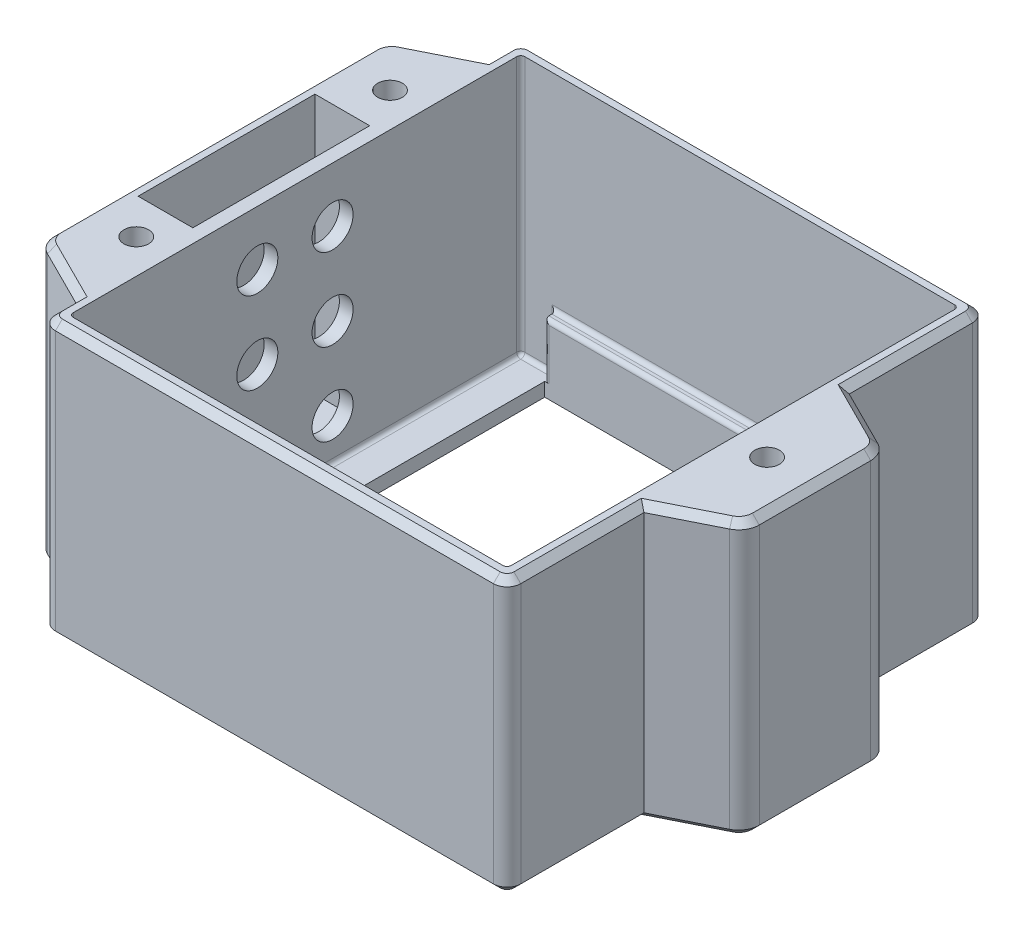
SolidWorks part; units mm, degrees
ref_plane "Front Plane" through (0, 0, 0) normal (0, 0, 1) x (1, 0, 0)
ref_plane "Top Plane" through (0, 0, 0) normal (0, 1, 0) x (1, 0, 0)
ref_plane "Right Plane" through (0, 0, 0) normal (1, 0, 0) x (0, 0, -1)
sketch "Sketch1" plane through (0, 0, 0) normal (0, 1, 0) x (1, 0, 0)
  line L0 (0, 36.2903) -> (0, -48.3871) construction
  line L1 (-53.2258, 0) -> (72.1774, 0) construction
  line L3 (-32, 35) -> (32, 35)
  line L4 (-34, 33) -> (-34, -33)
  line L5 (-32, -35) -> (32, -35)
  line L6 (34, 33) -> (34, -33)
  arc A0 (32, 35) -> (34, 33) centre (32, 33) cw
  arc A1 (32, -35) -> (34, -33) centre (32, -33) ccw
  arc A2 (-34, -33) -> (-32, -35) centre (-32, -33) ccw
  arc A3 (-32, 35) -> (-34, 33) centre (-32, 33) ccw
  point P9 (-50, 28.8306)
  point P10 (0, 0)
  point P11 (0, 0)
  point P14 (34, 35)
  point P17 (34, -35)
  point P22 (-34, 35)
  dimension "D3" = 2
  dimension "D1" = 68
  dimension "D2" = 70
extrude "Boss-Extrude1" add sketch "Sketch1" along normal blind 40
shell "Shell1" thickness 2 removed face at (0, 40, 0)
sketch "Sketch2" plane through (0, 0, 0) normal (0, 1, 0) x (1, 0, 0)
  line L1 (-34, 30) -> (-42.3416, 25.8292)
  line L2 (-44, 23.1459) -> (-44, -23.1459)
  line L3 (-42.3416, -25.8292) -> (-34, -30)
  line L4 (34, 15) -> (42.3416, 10.8292)
  line L6 (44, 8.1459) -> (44, -8.1459)
  line L7 (42.3416, -10.8292) -> (34, -15)
  line L9 (38.345, 0) -> (52.7567, 0) construction
  line L10 (-59.946, 0) -> (-25.6629, 0) construction
  line L11 (-34, 30) -> (-34, -30)
  line L12 (34, -15) -> (34, 15)
  line L13 (-1.2597, 0) -> (7.6725, 0) construction
  circle A0 centre (-37, 18.8964) radius 1.8
  circle A1 centre (-37, -18.1929) radius 1.8
  circle A2 centre (37, 0) radius 1.8
  arc A3 (42.3416, 10.8292) -> (44, 8.1459) centre (41, 8.1459) cw
  arc A4 (44, -8.1459) -> (42.3416, -10.8292) centre (41, -8.1459) cw
  arc A5 (-44, -23.1459) -> (-42.3416, -25.8292) centre (-41, -23.1459) ccw
  arc A6 (-42.3416, 25.8292) -> (-44, 23.1459) centre (-41, 23.1459) ccw
  point P15 (0, 0)
  point P16 (0, 0)
  point P29 (44, 10)
  point P32 (44, -10)
  point P35 (-44, -25)
  point P38 (-44, 25)
  dimension "D8" = 3.6
  dimension "D11" = 3
  dimension "D1" = 5
  dimension "D2" = 5
  dimension "D3" = 20
  dimension "D4" = 5
  dimension "D5" = 5
  dimension "D9" = 7
  dimension "D10" = 7
extrude "Boss-Extrude2" add sketch "Sketch2" along normal up to surface (40 mm away) up to face at (0, 40, 0)
sketch "Sketch3" plane through (0, 0, 0) normal (0, 1, 0) x (1, 0, 0)
  line L0 (16.0321, 0) -> (-16.7001, 0) construction
  line L1 (-34, 12.9227) -> (-42, 12.9227)
  line L3 (-42, 12.9227) -> (-42, -12.9227)
  line L4 (-42, -12.9227) -> (-34, -12.9227)
  line L5 (-44, -23.1459) -> (-44, 23.1459) construction
  line L6 (-34, 12.9227) -> (-34, -12.9227)
  line L7 (-32, 33) -> (-32, -33) construction
  point P5 (-33.4664, -12.9227)
  dimension "D1" = 2
  dimension "D2" = 90
  dimension "D3" = 2
extrude "Cut-Extrude1" cut sketch "Sketch3" against normal blind 38 from surface starting at face at (0, 40, 0)
sketch "Sketch4" plane through (-34, 0, 0) normal (-1, 0, 0) x (0, 0, 1)
  line L0 (0, -1.6893) -> (0, 13.6598) construction
  line L1 (-10.0101, 0) -> (9.8921, 0) construction
  circle A0 centre (-5.5, 32) radius 3
  circle A1 centre (5.5, 32) radius 3
  circle A2 centre (-5.5, 20) radius 3
  circle A3 centre (5.5, 20) radius 3
  circle A4 centre (-5.5, 8) radius 3
  circle A5 centre (5.5, 8) radius 3
  point P17 (0, 0)
  point P18 (0, 0)
  point P19 (0, 0)
  point P20 (0, 0)
  point P21 (0, 0)
  point P22 (0, 0)
  dimension "D1" = 6
  dimension "D2" = 11
  dimension "D3" = 8
  dimension "D4" = 12
  dimension "D5" = 12
extrude "Cut-Extrude2" cut sketch "Sketch4" against normal up to surface (2 mm away) up to face at (-32, 21, 0)
sketch "Sketch5" plane through (0, 0, 0) normal (0, 1, 0) x (1, 0, 0)
  line L0 (0, 14.4098) -> (0, -14.3144) construction
  line L1 (-17.4635, 0) -> (19.563, 0) construction
  line L2 (32, -33) -> (32, 33) construction
  line L3 (-26.85, 31.35) -> (30.4, 31.35)
  line L4 (-26.85, 31.35) -> (-26.85, -31.35)
  line L5 (-26.85, -31.35) -> (30.4, -31.35)
  line L6 (30.4, 31.35) -> (30.4, -31.35)
  line L8 (-32, 33) -> (-32, -33) construction
  point P9 (0, 0)
  dimension "D1" = 57.25
  dimension "D2" = 62.7
  dimension "D3" = 1.6
  dimension "D4" = 5.15
extrude "Cut-Extrude3" cut sketch "Sketch5" along normal up to surface (2 mm away) up to face at (0, 2, 0)
sketch "Sketch6" plane through (0, 2, 0) normal (0, 1, 0) x (1, 0, 0)
  line L0 (-26.85, 31.35) -> (-26.85, 33)
  line L1 (32, 33) -> (-32, 33) construction
  line L2 (-26.85, 33) -> (32, 33)
  line L3 (32, 33) -> (32, -33)
  line L4 (32, -33) -> (-26.85, -33)
  line L5 (-32, -33) -> (32, -33) construction
  line L6 (-26.85, -33) -> (-26.85, -31.35)
  line L7 (-26.85, -31.35) -> (30.4, -31.35)
  line L8 (30.4, -31.35) -> (30.4, 31.35)
  line L9 (30.4, 31.35) -> (-26.85, 31.35)
extrude "Boss-Extrude3" add sketch "Sketch6" along normal blind 8
chamfer "Chamfer1" distance 1 angle 45 40 edges at (34, 40, -24) (-34, 40, -31.5) (33.4142, 40, -34.4142) (-33.4142, 40, -34.4142) (0, 40, -35) (-34, 40, 31.5) (34, 40, 24) (-33.4142, 40, 34.4142) (33.4142, 40, 34.4142) (0, 40, 35) (38.1708, 40, -12.9146) (38.1708, 40, 12.9146) (43.552, 40, -9.7231) (43.552, 40, 9.7231) (44, 40, 0) (-38.1708, 40, 27.9146) (-43.552, 40, 24.7231) (-44, 40, 0) (-43.552, 40, -24.7231) (-38.1708, 40, -27.9146) (-38.1708, 0, 27.9146) (-34, 0, 31.5) (34, 0, -24) (44, 0, 0) (38.1708, 0, -12.9146) (43.552, 0, -9.7231) (43.552, 0, 9.7231) (34, 0, 24) (38.1708, 0, 12.9146) (-33.4142, 0, 34.4142) (33.4142, 0, 34.4142) (0, 0, 35) (33.4142, 0, -34.4142) (-43.552, 0, 24.7231) (0, 0, -35) (-33.4142, 0, -34.4142) (-34, 0, -31.5) (-38.1708, 0, -27.9146) (-43.552, 0, -24.7231) (-44, 0, 0)
fillet "Fillet1" radius 0.6 17 edges at (-32, 2, 0) (2.575, 10, -33) (-26.85, 6, -33) (-26.85, 6, 33) (-29.425, 2, 33) (-29.425, 2, -33) (32, 10, 0) (2.575, 10, 33) (1.775, 10, 31.35) (30.4, 10, 0) (1.775, 10, -31.35) (-26.85, 6, -31.35) (-26.85, 6, 31.35) (-32, 21, 33) (-32, 21, -33) (32, 25, -33) (32, 25, 33)
sketch "Sketch7" plane through (0, 0, 0) normal (0, -1, 0) x (1, 0, 0)
  line L0 (-33, 29.382) -> (-33, 33)
  line L1 (-32, 34) -> (32, 34)
  line L2 (33, 33) -> (33, 14.382)
  line L3 (33, 14.382) -> (41.8944, 9.9348)
  line L4 (43, 8.1459) -> (43, -8.1459)
  line L5 (41.8944, -9.9348) -> (33, -14.382)
  line L6 (33, -14.382) -> (33, -33)
  line L7 (32, -34) -> (-32, -34)
  line L8 (-33, -33) -> (-33, -29.382)
  line L9 (-33, -29.382) -> (-41.8944, -24.9348)
  line L10 (-43, -23.1459) -> (-43, 23.1459)
  line L11 (-41.8944, 24.9348) -> (-33, 29.382)
  line L13 (-26.85, -31.35) -> (30.4, -31.35)
  line L14 (-26.85, -31.35) -> (-26.85, 31.35)
  line L15 (-26.85, 31.35) -> (30.4, 31.35)
  line L16 (30.4, -31.35) -> (30.4, 31.35)
  arc A1 (-41.8944, -24.9348) -> (-43, -23.1459) centre (-41, -23.1459) cw
  arc A2 (-43, 23.1459) -> (-41.8944, 24.9348) centre (-41, 23.1459) cw
  arc A3 (41.8944, 9.9348) -> (43, 8.1459) centre (41, 8.1459) cw
  arc A4 (43, -8.1459) -> (41.8944, -9.9348) centre (41, -8.1459) cw
  arc A5 (-32, -34) -> (-33, -33) centre (-32, -33) cw
  arc A6 (33, -33) -> (32, -34) centre (32, -33) cw
  arc A7 (32, 34) -> (33, 33) centre (32, 33) cw
  arc A8 (-33, 33) -> (-32, 34) centre (-32, 33) cw
  circle A9 centre (-37, 18.1929) radius 1.8
  circle A10 centre (-37, -18.8964) radius 1.8
  circle A11 centre (37, 0) radius 1.8
  circle A12 centre (37, 0) radius 1.8 construction
  point P25 (-43, -24.382)
  point P30 (-43, 24.382)
  point P55 (37.0737, 0)
  dimension "D1" = 2
  dimension "D2" = 1
